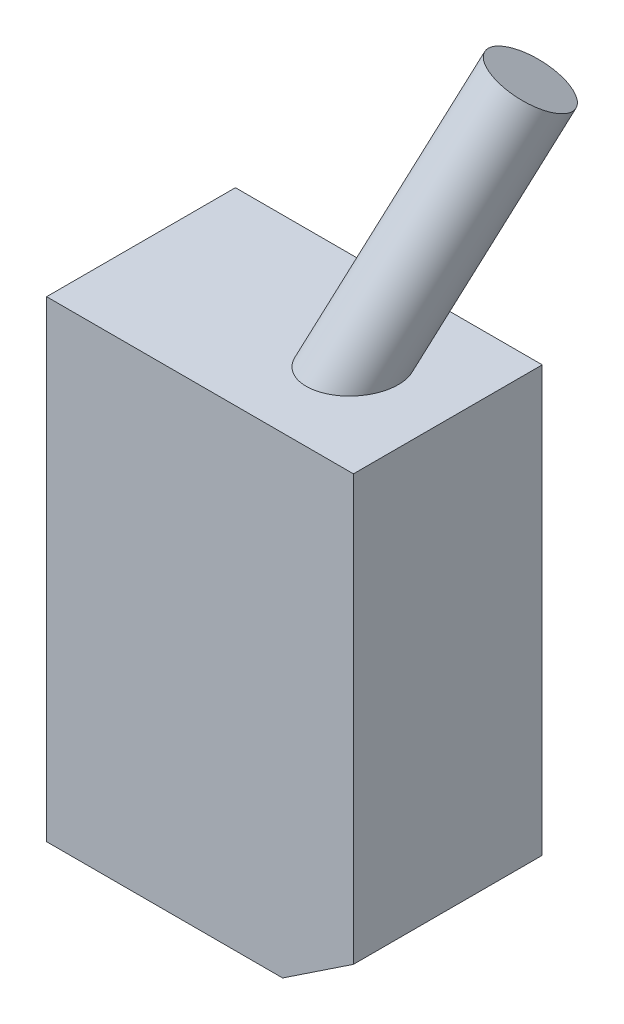
SolidWorks part; units mm, degrees
ref_plane "Front Plane" through (0, 0, 0) normal (0, 0, 1) x (1, 0, 0)
ref_plane "Top Plane" through (0, 0, 0) normal (0, 1, 0) x (1, 0, 0)
ref_plane "Right Plane" through (0, 0, 0) normal (1, 0, 0) x (0, 0, -1)
sketch "Sketch1" plane through (0, 0, 0) normal (0, 1, 0) x (1, 0, 0)
  line L1 (-82.55, -50.8) -> (82.55, -50.8)
  line L2 (-82.55, -50.8) -> (-82.55, 50.8)
  line L3 (-82.55, 50.8) -> (82.55, 50.8)
  line L4 (82.55, -50.8) -> (82.55, 50.8)
  line L5 (-82.55, -50.8) -> (82.55, 50.8) construction
  line L6 (-82.55, 50.8) -> (82.55, -50.8) construction
  point P0 (0, 0)
  dimension "D1" = 165.1
  dimension "D2" = 101.6
extrude "Boss-Extrude1" add sketch "Sketch1" along normal blind 254
sketch "Sketch2" plane through (0, 0, -50.8) normal (0, 0, -1) x (-1, 0, 0)
  line L0 (-44.45, 0) -> (-82.55, 25.4)
  line L1 (-82.55, 0) -> (82.55, 0) construction
  line L2 (-82.55, 254) -> (-82.55, 0) construction
  line L3 (-82.55, 25.4) -> (-82.55, 0)
  line L4 (-82.55, 0) -> (-44.45, 0)
  dimension "D1" = 25.4
  dimension "D2" = 127
extrude "Cut-Extrude1" cut sketch "Sketch2" against normal blind 254
sketch3d "3DSketch1"
  line L0 (49.8123, 254, 0) -> (104.0644, 254, 0) construction
  line L1 (31.75, 254, 0) -> (31.75, 254, -50000) construction
  line L2 (82.55, 254, 50.8) -> (82.55, 254, -50.8) construction
  line L3 (-82.55, 254, 50.8) -> (82.55, 254, 50.8) construction
  line L4 (31.75, 254, 0) -> (31.75, 50254, 0) construction
  line L5 (31.75, 254, 0) -> (71.194, 386.3694, -64.407)
  point P4 (31.75, 254, 0)
  dimension "D1" = 50.8
  dimension "D2" = 50.8
  dimension "D3" = 75
  dimension "D4" = 65
  dimension "D5" = 152.4
ref_plane "Plane3" through (31.75, 254, 0) normal (0.2588, 0.8686, -0.4226) x (0.9658, -0.24, 0.0983)
sketch "Sketch5" plane through (31.75, 254, 0) normal (0.2588, 0.8686, -0.4226) x (0.9658, -0.24, 0.0983)
  circle A0 centre (0, 0) radius 20.447
  dimension "D1" = 40.894
extrude "Boss-Extrude3" add sketch "Sketch5" along normal blind 139.7 and the other way up to surface other way up to face at (0, 254, 0)
